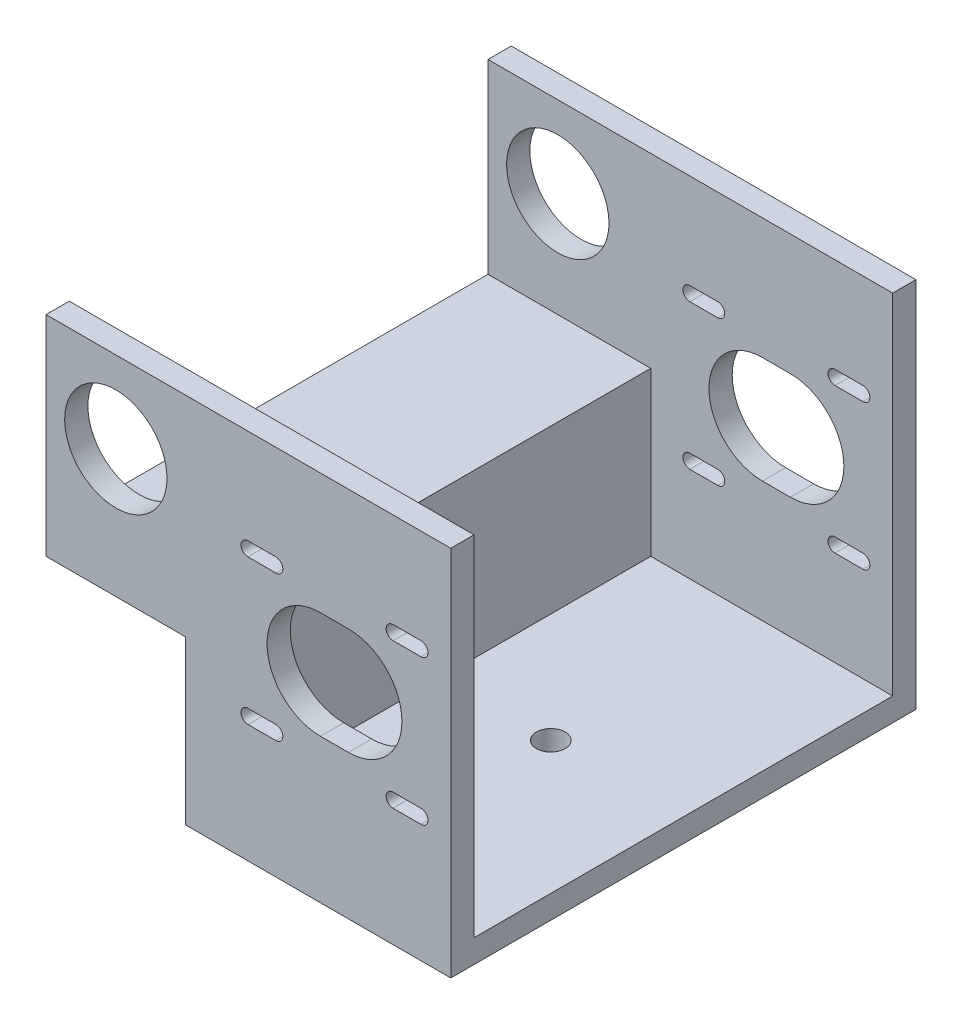
SolidWorks part; units mm, degrees
ref_plane "Front Plane" through (0, 0, 0) normal (0, 0, 1) x (1, 0, 0)
ref_plane "Top Plane" through (0, 0, 0) normal (0, 1, 0) x (1, 0, 0)
ref_plane "Right Plane" through (0, 0, 0) normal (1, 0, 0) x (0, 0, -1)
sketch "Sketch1" plane through (0, 0, 0) normal (0, 1, 0) x (1, 0, 0)
  line L1 (-28.5, 50) -> (28.5, 50)
  line L2 (-28.5, 50) -> (-28.5, -50)
  line L3 (-28.5, -50) -> (28.5, -50)
  line L4 (28.5, 50) -> (28.5, -50)
  line L5 (-28.5, 50) -> (28.5, -50) construction
  line L6 (-28.5, -50) -> (28.5, 50) construction
  point P0 (0, 0)
  dimension "D1" = 100
  dimension "D2" = 57
extrude "Boss-Extrude1" add sketch "Sketch1" along normal blind 80
sketch "Sketch3" plane through (28.5, 40, 0) normal (-1, 0, 0) x (0, 1, 0)
  line L1 (40, 45) -> (-35, 45)
  line L2 (40, 45) -> (40, -45)
  line L3 (40, -45) -> (-35, -45)
  line L4 (-35, 45) -> (-35, -45)
  line L5 (40, 45) -> (-35, -45) construction
  line L6 (40, -45) -> (-35, 45) construction
  line L10 (40, -50) -> (40, 50) construction
  line L11 (-40, -50) -> (-40, 50) construction
  line L12 (40, 50) -> (-40, 50) construction
  line L13 (40, -50) -> (-40, -50) construction
  point P0 (2.5, 0)
  dimension "D1" = 5
  dimension "D2" = 5
  dimension "D3" = 5
extrude "Cut-Extrude1" cut sketch "Sketch3" along normal blind 52
sketch "Sketch4" plane through (-40, 5, 0) normal (0, -1, 0) x (-1, 0, 0)
  line L0 (-40, 0) -> (-40, 10) construction
  circle A0 centre (-40, 0) radius 3.1
  circle A1 centre (-40, 10) radius 1.5 construction
  circle A2 centre (-30, 0) radius 1.5 construction
  circle A3 centre (-40, -10) radius 1.5 construction
  circle A4 centre (-50, 0) radius 1.5 construction
  dimension "D1" = 6.2
  dimension "D2" = 3
  dimension "D3" = 10
  dimension "D4" = 4
extrude "Cut-Extrude2" cut sketch "Sketch4" along normal through all
sketch "Sketch7" plane through (-28.5, 0, 0) normal (-1, 0, 0) x (0, 0, 1)
  line L0 (50, 80) -> (50, 0) construction
  line L1 (-50, 80) -> (-45, 80)
  line L2 (-50, 80) -> (-50, 35)
  line L4 (-45, 80) -> (-45, 40)
  line L5 (50, 80) -> (45, 80)
  line L6 (50, 80) -> (50, 35)
  line L8 (45, 80) -> (45, 40)
  line L9 (-50, 80) -> (50, 80) construction
  line L11 (-45, 40) -> (45, 40)
  line L13 (-50, 35) -> (50, 35)
  dimension "D1" = 5
  dimension "D2" = 40
  dimension "D3" = 5
extrude "Boss-Extrude2" add sketch "Sketch7" along normal blind 30
sketch "Sketch8" plane through (-28.5, 0, 0) normal (-1, 0, 0) x (0, 0, 1)
  line L4 (-45, 80) -> (-45, 40)
  line L5 (-45, 40) -> (45, 40)
  line L6 (45, 40) -> (45, 80)
  line L7 (45, 80) -> (-45, 80)
  line L8 (-45, 80) -> (-45, 40)
  line L9 (-45, 40) -> (45, 40)
  line L10 (45, 40) -> (45, 80)
  line L11 (45, 80) -> (-45, 80)
  dimension "D1" = 0
extrude "Cut-Extrude5" cut sketch "Sketch8" against normal up to next
sketch "Sketch5" plane through (0, 0, -50) normal (0, 0, -1) x (-1, 0, 0)
  line L0 (-3.5, 42.5) -> (31.0759, 42.5) construction
  line L1 (-3.5, 42.5) -> (-3.5, 17.143) construction
  line L2 (-28.5, 80) -> (58.5, 80) construction
  line L3 (-28.5, 80) -> (58.5, 80) construction
  line L4 (58.5, 80) -> (58.5, 35) construction
  line L5 (-22.1, 58.1) -> (-16.1, 58.1) construction
  line L6 (-22.1, 59.6) -> (-16.1, 59.6)
  line L7 (-22.1, 56.6) -> (-16.1, 56.6)
  line L8 (-28.5, 80) -> (-28.5, 0) construction
  line L9 (-0.5, 42.5) -> (-6.5, 42.5) construction
  line L10 (-0.5, 31) -> (-6.5, 31)
  line L11 (-0.5, 54) -> (-6.5, 54)
  line L12 (-22.1, 26.9) -> (-16.1, 26.9) construction
  line L13 (-22.1, 25.4) -> (-16.1, 25.4)
  line L14 (-22.1, 28.4) -> (-16.1, 28.4)
  line L15 (15.1, 26.9) -> (9.1, 26.9) construction
  line L16 (15.1, 25.4) -> (9.1, 25.4)
  line L17 (15.1, 28.4) -> (9.1, 28.4)
  line L18 (15.1, 58.1) -> (9.1, 58.1) construction
  line L19 (15.1, 59.6) -> (9.1, 59.6)
  line L20 (15.1, 56.6) -> (9.1, 56.6)
  circle A5 centre (43.5, 62.5) radius 11
  arc A7 (-22.1, 59.6) -> (-22.1, 56.6) centre (-22.1, 58.1) ccw
  arc A8 (-16.1, 56.6) -> (-16.1, 59.6) centre (-16.1, 58.1) ccw
  arc A9 (-0.5, 31) -> (-0.5, 54) centre (-0.5, 42.5) ccw
  arc A10 (-6.5, 54) -> (-6.5, 31) centre (-6.5, 42.5) ccw
  arc A11 (-22.1, 25.4) -> (-22.1, 28.4) centre (-22.1, 26.9) cw
  arc A12 (-16.1, 28.4) -> (-16.1, 25.4) centre (-16.1, 26.9) cw
  arc A13 (15.1, 25.4) -> (15.1, 28.4) centre (15.1, 26.9) ccw
  arc A14 (9.1, 28.4) -> (9.1, 25.4) centre (9.1, 26.9) ccw
  arc A15 (15.1, 59.6) -> (15.1, 56.6) centre (15.1, 58.1) cw
  arc A16 (9.1, 56.6) -> (9.1, 59.6) centre (9.1, 58.1) cw
  point P2 (-19.1, 58.1)
  point P8 (-19.1, 42.5)
  point P13 (-3.5, 42.5)
  point P31 (-19.1, 26.9)
  point P38 (12.1, 26.9)
  point P45 (12.1, 58.1)
  dimension "D5" = 15.6
  dimension "D8" = 6
  dimension "D9" = 22
  dimension "D2" = 1.5
  dimension "D7" = 11.5
  dimension "D12" = 25
  dimension "D3" = 15.6
  dimension "D4" = 6
  dimension "D6" = 37.5
  dimension "D10" = 17.5
  dimension "D11" = 15
extrude "Cut-Extrude3" cut sketch "Sketch5" against normal through all
